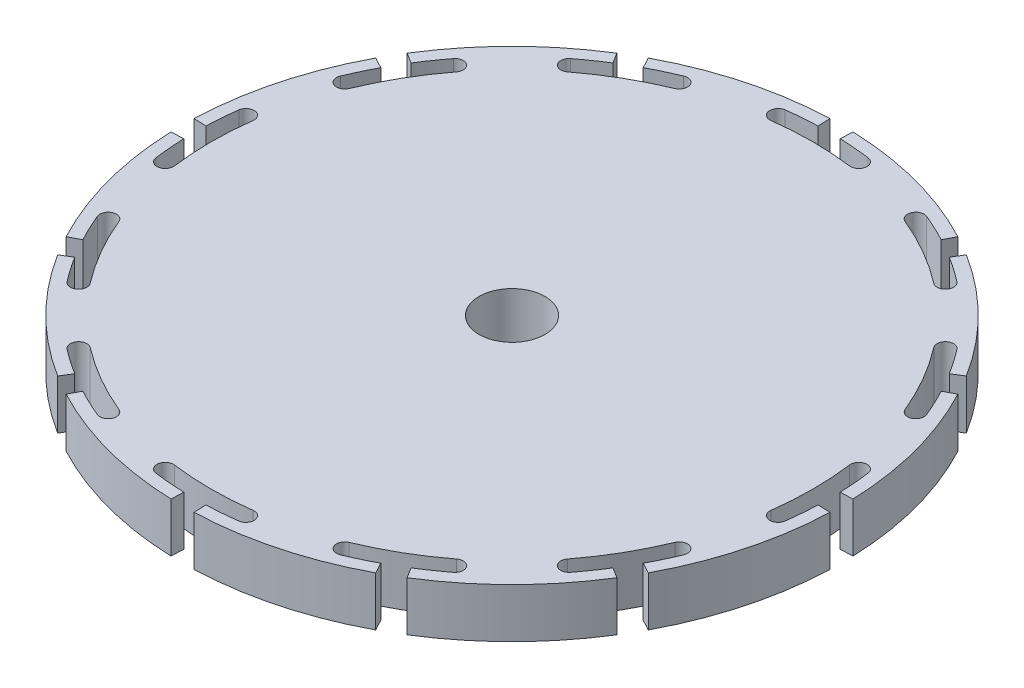
SolidWorks part; units mm, degrees
ref_plane "Front Plane" through (0, 0, 0) normal (0, 0, 1) x (1, 0, 0)
ref_plane "Top Plane" through (0, 0, 0) normal (0, 1, 0) x (1, 0, 0)
ref_plane "Right Plane" through (0, 0, 0) normal (1, 0, 0) x (0, 0, -1)
sketch "Sketch1" plane through (0, 0, 0) normal (0, 1, 0) x (1, 0, 0)
  circle A0 centre (0, 0) radius 40
  dimension "D1" = 80
sketch "Sketch2" plane through (0, 0, 0) normal (0, 1, 0) x (1, 0, 0)
  line L0 (0, 0) -> (0, 40) construction
  line L1 (-1.396, 39.9756) -> (0, 0) construction
  line L2 (0, 0) -> (-5.221, 39.6578) construction
  line L3 (-1.396, 39.9756) -> (-1.3436, 38.4765)
  line L4 (0, 0) -> (5.221, 39.6578) construction
  line L5 (1.396, 39.9756) -> (0, 0) construction
  line L6 (1.396, 39.9756) -> (1.3436, 38.4765)
  arc A0 (4.7642, 36.1877) -> (-4.7642, 36.1877) centre (0, 0) ccw
  circle A1 centre (0, 0) radius 40 construction
  arc A2 (-1.396, 39.9756) -> (1.396, 39.9756) centre (0, 0) cw
  arc A3 (-1.3436, 38.4765) -> (-5.0253, 38.1706) centre (0, 0) ccw
  arc A4 (-4.7642, 36.1877) -> (-5.0253, 38.1706) centre (-4.8947, 37.1792) cw
  arc A5 (4.7642, 36.1877) -> (5.0253, 38.1706) centre (4.8947, 37.1792) ccw
  arc A6 (1.3436, 38.4765) -> (5.0253, 38.1706) centre (0, 0) cw
  point P130 (0, 0)
  dimension "D1" = 15
  dimension "D2" = 2
  dimension "D4" = 1.5
  dimension "D3" = 4
sketch "Sketch3" plane through (0, 0, 0) normal (0, 1, 0) x (1, 0, 0)
  circle A0 centre (0, 0) radius 4
  dimension "D1" = 8
extrude "Wheel Blank" add sketch "Sketch1" along normal blind 6
extrude "T-Slot" cut sketch "Sketch2" along normal through all
pattern_circular "CirPattern1" count 12 over 360 about axis through (0, 6, 0) along (0, -1, 0) of "T-Slot"
extrude "Center Hole" cut sketch "Sketch3" along normal blind 6
